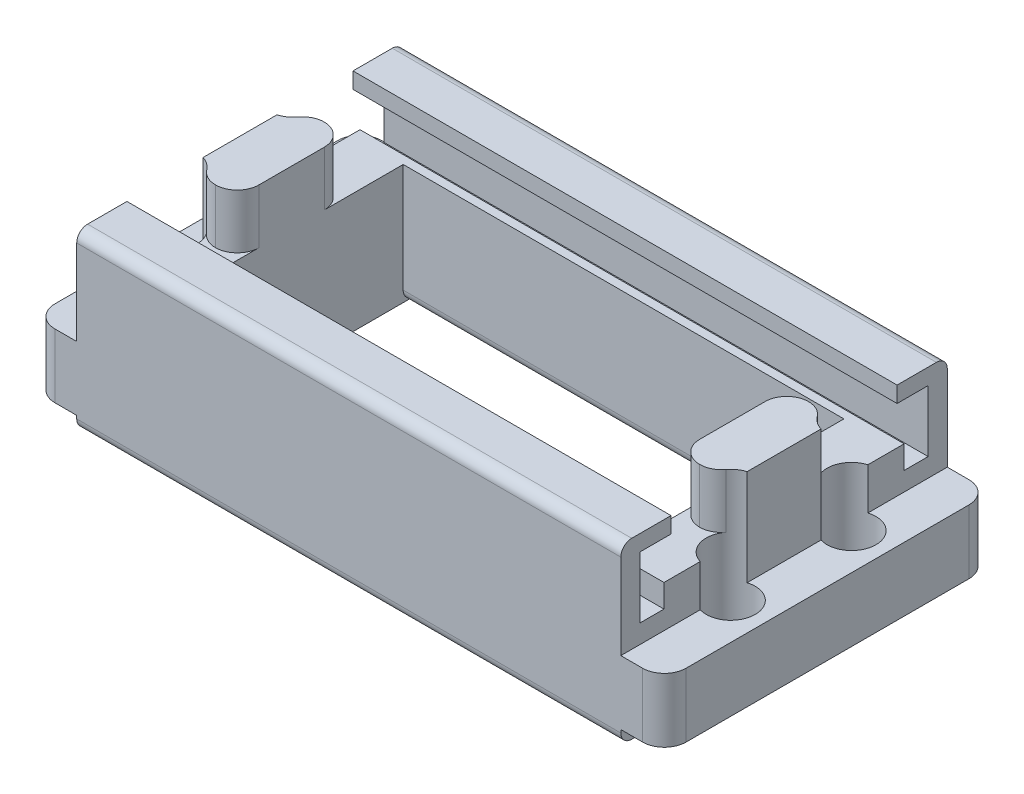
SolidWorks part; units mm, degrees
ref_plane "Front Plane" through (0, 0, 0) normal (0, 0, 1) x (1, 0, 0)
ref_plane "Top Plane" through (0, 0, 0) normal (0, 1, 0) x (1, 0, 0)
ref_plane "Right Plane" through (0, 0, 0) normal (1, 0, 0) x (0, 0, -1)
sketch "Sketch1" plane through (0, 0, 0) normal (0, 1, 0) x (1, 0, 0)
  line L1 (0, 0) -> (50, 0)
  line L2 (0, 0) -> (0, 30)
  line L3 (0, 30) -> (50, 30)
  line L4 (50, 0) -> (50, 30)
  dimension "D1" = 30
  dimension "D2" = 50
extrude "Boss-Extrude1" add sketch "Sketch1" along normal blind 16
sketch "Sketch2" plane through (0, 16, 0) normal (0, 1, 0) x (1, 0, 0)
  line L0 (0, 30) -> (0, 0) construction
  line L1 (4.75, 25.25) -> (45.25, 25.25)
  line L2 (4.75, 25.25) -> (4.75, 4.75)
  line L3 (4.75, 4.75) -> (45.25, 4.75)
  line L4 (45.25, 25.25) -> (45.25, 4.75)
  line L5 (50, 0) -> (50, 30) construction
  line L6 (0, 0) -> (50, 0) construction
  line L7 (50, 30) -> (0, 30) construction
  dimension "D1" = 4.75
  dimension "D2" = 4.75
  dimension "D3" = 40.5
  dimension "D4" = 4.75
  dimension "D5" = 4.75
  dimension "D6" = 20.5
extrude "Cut-Extrude1" cut sketch "Sketch2" against normal through all
sketch "Sketch3" plane through (0, 0, 0) normal (0, -1, 0) x (1, 0, 0)
  line L0 (50, -15) -> (0, -15) construction
  line L1 (50, 0) -> (50, -30) construction
  line L2 (0, -30) -> (0, 0) construction
  line L3 (-0.6115, -16.05) -> (4.75, -16.05)
  line L4 (-0.6115, -16.05) -> (-0.6115, -13.95)
  line L5 (4.75, -16.05) -> (4.75, -13.95)
  line L6 (-0.6115, -13.95) -> (4.75, -13.95)
  line L7 (-0.6115, -16.05) -> (4.75, -13.95) construction
  line L8 (4.75, -16.05) -> (-0.6115, -13.95) construction
  line L12 (50.3622, -13.95) -> (44.3622, -13.95)
  line L13 (50.3622, -13.95) -> (50.3622, -16.05)
  line L14 (44.3622, -13.95) -> (44.3622, -16.05)
  line L15 (50.3622, -16.05) -> (44.3622, -16.05)
  line L16 (50.3622, -13.95) -> (44.3622, -16.05) construction
  line L17 (44.3622, -13.95) -> (50.3622, -16.05) construction
  point P7 (2.0693, -15)
  point P14 (47.3622, -15)
  dimension "D1" = 5.3615
  dimension "D2" = 2.1
  dimension "D3" = 6
  dimension "D4" = 2.1
extrude "Cut-Extrude2" cut sketch "Sketch3" against normal blind 1.25
ref_plane "Plane1" through (0, 0, -15) normal (0, 0, -1) x (-1, 0, 0)
ref_plane "Plane2" through (25, 0, 0) normal (1, 0, 0) x (0, 0, -1)
sketch "Sketch5" plane through (50, 0, 0) normal (1, 0, 0) x (0, 0, -1)
  line L0 (30, 16) -> (30, 0) construction
  line L1 (30, 1.2785) -> (0, 1.2785)
  line L2 (30, 1.2785) -> (30, 7.1598)
  line L3 (30, 7.1598) -> (0, 7.1598)
  line L4 (0, 1.2785) -> (0, 7.1598)
  line L5 (0, 16) -> (0, 0) construction
extrude "Boss-Extrude2" add sketch "Sketch5" along normal blind 4
mirror "Mirror1" about plane through (25, 0, 0) normal (1, 0, 0) of "Boss-Extrude2"
sketch "Sketch4" plane through (0, 0, 0) normal (0, -1, 0) x (1, 0, 0)
  line L0 (45.25, -16.05) -> (45.25, -25.25) construction
  line L5 (45.25, -16.05) -> (50, -16.05) construction
  line L12 (-5.1527, -15) -> (65.2416, -15) construction
  line L13 (-8.8, -15) -> (8.8, -15) construction
  line L14 (25, 3.466) -> (25, -38.7311) construction
  line L15 (25, -3.7355) -> (25, 3.7355) construction
  circle A0 centre (50.65, -20.55) radius 2.25
  circle A1 centre (-0.65, -20.55) radius 2.25
  circle A2 centre (50.65, -9.45) radius 2.25
  circle A3 centre (-0.65, -9.45) radius 2.25
  dimension "D1" = 4.5
  dimension "D2" = 5.4
  dimension "D3" = 4.5
extrude "Cut-Extrude3" cut sketch "Sketch4" against normal through all
sketch "Sketch7" plane through (50, 0, 0) normal (1, 0, 0) x (0, 0, -1)
  line L1 (26.0332, 11) -> (20, 11)
  line L2 (28.2416, 11) -> (28.2416, 14.5309)
  line L3 (28.2416, 14.5309) -> (25.387, 14.5309)
  line L5 (22.7041, 0) -> (30, 0) construction
  line L6 (20, 11) -> (20, 19.2535)
  line L7 (25.387, 14.5309) -> (25.387, 19.2535)
  line L8 (25.387, 19.2535) -> (20, 19.2535)
  line L11 (28.2416, 11) -> (28.2416, 8.8809)
  line L12 (28.2416, 8.8809) -> (26.0332, 8.8809)
  line L13 (26.0332, 11) -> (26.0332, 8.8809)
  dimension "D1" = 11
extrude "Cut-Extrude4" cut sketch "Sketch7" against normal through all
mirror "Mirror2" about plane through (0, 0, -15) normal (0, 0, -1) of "Cut-Extrude4"
fillet "Fillet1" radius 1 6 edges at (25, 0, -30) (25, 0, 0) (25, 0, -4.75) (25, 0, -25.25) (25, 16, 0) (25, 16, -30)
fillet "Fillet2" radius 2 4 edges at (-4, 4.2192, -30) (-4, 4.2192, 0) (54, 4.2192, 0) (54, 4.2192, -30)
fillet "Fillet3" radius 2 8 edges at (1.5317, 13.5, -10) (4.75, 13.5, -10) (1.5317, 13.5, -20) (4.75, 13.5, -20) (45.25, 13.5, -10) (48.4683, 13.5, -10) (45.25, 13.5, -20) (48.4683, 13.5, -20)
